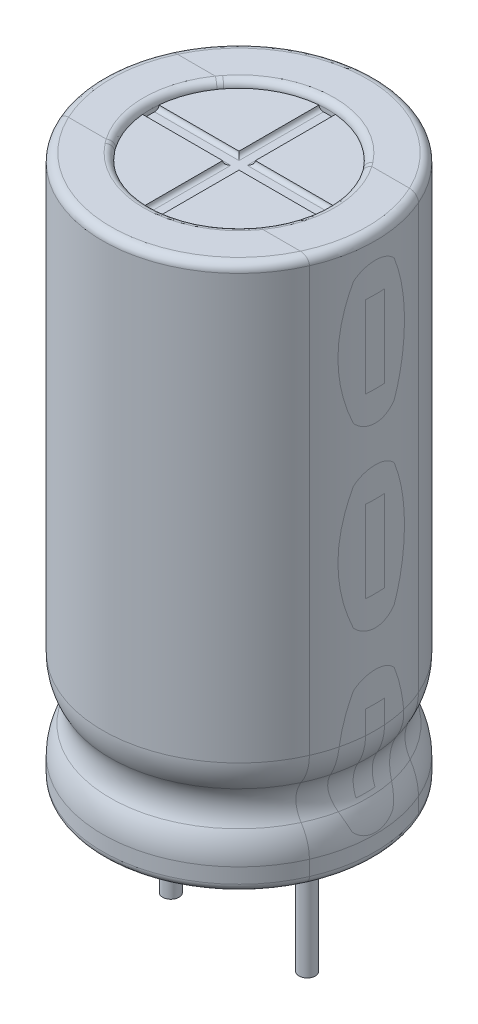
SolidWorks part; units mm, degrees
ref_plane "Front Plane" through (0, 0, 0) normal (0, 0, 1) x (1, 0, 0)
ref_plane "Top Plane" through (0, 0, 0) normal (0, 1, 0) x (1, 0, 0)
ref_plane "Right Plane" through (0, 0, 0) normal (1, 0, 0) x (0, 0, -1)
sketch "Эскиз1" plane through (0, 0, 0) normal (0, 0, 1) x (1, 0, 0)
  line L0 (0, 47.0384) -> (0, -50.5015) construction
  line L1 (0, 0) -> (-5, 0)
  line L2 (-5, 0) -> (-5, 1.5395)
  line L3 (-5, 20) -> (0, 20)
  line L4 (0, 20) -> (0, 0)
  line L5 (-5, 3.4605) -> (-5, 20)
  arc A0 (-5, 1.5395) -> (-5, 3.4605) centre (-5.8, 2.5) ccw
  dimension "D3" = 2.5
  dimension "D1" = 5
  dimension "D2" = 20
  dimension "D4" = 0.8
  dimension "D5" = 2.5
revolve "Повернуть2" add sketch "Эскиз1" angle 360 about L0
sketch "Эскиз2" plane through (0, 20, 0) normal (0, 1, 0) x (1, 0, 0)
  circle A0 centre (0, 0) radius 3.25
  dimension "D1" = 6.5
extrude "Вырез-Вытянуть1" cut sketch "Эскиз2" against normal blind 0.25
sketch "Эскиз3" plane through (0, 19.75, 0) normal (0, 1, 0) x (1, 0, 0)
  line L0 (0, 5.3403) -> (0, -5.4999) construction
  line L1 (-5.5664, 0) -> (5.593, 0) construction
  line L2 (-0.3, 3.2361) -> (-0.3, 0.3)
  line L3 (-0.3, 0.3) -> (-3.2361, 0.3)
  line L4 (0.3, 0.3) -> (3.2361, 0.3)
  line L5 (0.3, 3.2361) -> (0.3, 0.3)
  line L6 (0.3, -0.3) -> (3.2361, -0.3)
  line L7 (0.3, -3.2361) -> (0.3, -0.3)
  line L8 (-0.3, -3.2361) -> (-0.3, -0.3)
  line L9 (-0.3, -0.3) -> (-3.2361, -0.3)
  circle A0 centre (0, 0) radius 3.25 construction
  arc A1 (-3.2361, 0.3) -> (-3.2361, -0.3) centre (0, 0) ccw
  arc A2 (0.3, 3.2361) -> (-0.3, 3.2361) centre (0, 0) ccw
  arc A3 (3.2361, -0.3) -> (3.2361, 0.3) centre (0, 0) ccw
  arc A4 (-0.3, -3.2361) -> (0.3, -3.2361) centre (0, 0) ccw
  dimension "D1" = 0.3
  dimension "D2" = 0.3
extrude "Вырез-Вытянуть2" cut sketch "Эскиз3" against normal blind 0.15
fillet "Скругление1" radius 0.3 2 edges at (0, 0, 5) (0, 20, 5)
fillet "Скругление2" radius 2 2 edges at (0, 1.5395, 5) (0, 3.4605, 5)
sketch "Эскиз4" plane through (0, 0, 0) normal (0, -1, 0) x (1, 0, 0)
  line L0 (0, 5.3536) -> (0, -5.5664) construction
  line L1 (-5.8457, 0) -> (5.2871, 0) construction
  circle A1 centre (0, 0) radius 3.25
  dimension "D1" = 6.5
extrude "Вырез-Вытянуть3" cut sketch "Эскиз4" against normal blind 0.25
sketch "Эскиз5" plane through (0, 0.25, 0) normal (0, -1, 0) x (1, 0, 0)
  line L0 (0, 5.3137) -> (0, -5.593) construction
  line L1 (-5.4467, 0) -> (5.3536, 0) construction
  circle A0 centre (-2.5, 0) radius 0.3
  circle A1 centre (2.5, 0) radius 0.3
  dimension "D1" = 0.6
  dimension "D2" = 2.5
extrude "Бобышка-Вытянуть1" add sketch "Эскиз5" along normal blind 5
fillet "Скругление3" radius 0.15 8 edges at (0.3, 19.6, -1.7681) (-1.7681, 19.6, 0.3) (1.7681, 19.6, 0.3) (0.3, 19.6, 1.7681) (-0.3, 19.6, 1.7681) (1.7681, 19.6, -0.3) (-0.3, 19.6, -1.7681) (-1.7681, 19.6, -0.3)
ref_plane "Плоскость1" through (5.5, 0, 0) normal (1, 0, 0) x (0, 0, -1)
sketch "Эскиз6" plane through (5.5, 0, 0) normal (1, 0, 0) x (0, 0, -1)
  line L0 (0, 22.3182) -> (0, -7.8953) construction
  line L1 (3.25, 20) -> (-3.25, 20) construction
  line L2 (-2, 25) -> (2, 25)
  line L3 (-2, 25) -> (-2, -5)
  line L4 (-2, -5) -> (2, -5)
  line L5 (2, 25) -> (2, -5)
  line L6 (-2, 25) -> (2, -5) construction
  line L7 (-2, -5) -> (2, 25) construction
  line L19 (4.7, 20) -> (-4.7, 20) construction
  line L20 (0.35, 18) -> (-0.35, 18)
  line L30 (0.35, 18) -> (0.35, 15)
  line L31 (0.35, 15) -> (-0.35, 15)
  line L32 (-0.35, 18) -> (-0.35, 15)
  line L33 (0.35, 18) -> (-0.35, 15) construction
  line L34 (0.35, 15) -> (-0.35, 18) construction
  line L35 (0.35, 11.5) -> (0.35, 8.5)
  line L36 (0.75, 18.75) -> (-0.75, 18.75) construction
  line L37 (0.75, 18.75) -> (0.75, 14.25) construction
  line L38 (0.75, 14.25) -> (-0.75, 14.25) construction
  line L39 (-0.75, 18.75) -> (-0.75, 14.25) construction
  line L40 (0.75, 18.75) -> (-0.75, 14.25) construction
  line L41 (0.75, 14.25) -> (-0.75, 18.75) construction
  line L42 (0.35, 11.5) -> (-0.35, 11.5)
  line L43 (-0.35, 11.5) -> (-0.35, 8.5)
  line L44 (0.35, 8.5) -> (-0.35, 8.5)
  line L45 (0.35, 5) -> (0.35, 2)
  line L46 (0.35, 5) -> (-0.35, 5)
  line L47 (-0.35, 5) -> (-0.35, 2)
  line L48 (0.35, 2) -> (-0.35, 2)
  arc A0 (0.75, 18.75) -> (0.75, 14.25) centre (-4.4006, 16.5) cw
  arc A1 (-0.75, 18.75) -> (-0.75, 14.25) centre (4.4006, 16.5) ccw
  arc A2 (0.75, 18.75) -> (-0.75, 18.75) centre (0, 18.0886) ccw
  arc A3 (-0.75, 14.25) -> (0.75, 14.25) centre (0, 14.9114) ccw
  arc A4 (-0.75, 7.75) -> (0.75, 7.75) centre (0, 8.4114) ccw
  arc A5 (0.75, 12.25) -> (0.75, 7.75) centre (-4.4006, 10) cw
  arc A6 (0.75, 12.25) -> (-0.75, 12.25) centre (0, 11.5886) ccw
  arc A7 (-0.75, 12.25) -> (-0.75, 7.75) centre (4.4006, 10) ccw
  arc A8 (-0.75, 1.25) -> (0.75, 1.25) centre (0, 1.9114) ccw
  arc A9 (0.75, 5.75) -> (0.75, 1.25) centre (-4.4006, 3.5) cw
  arc A10 (0.75, 5.75) -> (-0.75, 5.75) centre (0, 5.0886) ccw
  arc A11 (-0.75, 5.75) -> (-0.75, 1.25) centre (4.4006, 3.5) ccw
  point P3 (0, 10)
  point P10 (0, 16.5)
  point P12 (0, 12.7929)
  point P18 (0, 16.5)
  point P27 (1.22, 16.5)
  point P28 (-1.22, 16.5)
  point P29 (0, 19.0886)
  point P30 (0, 13.9114)
  dimension "D9" = 0.78
  dimension "D1" = 30
  dimension "D2" = 4
  dimension "D3" = 5
  dimension "D4" = 2
  dimension "D5" = 3
  dimension "D6" = 0.7
  dimension "D7" = 4.5
  dimension "D8" = 1.5
  dimension "D10" = 0.78
  dimension "D11" = 1
  dimension "D12" = 1
  dimension "D13" = 3
split line "Разделяющая линия1"
fillet "Скругление4" radius 0.25 4 edges at (-3.25, 20, 0) (0, 20, 3.25) (3.25, 20, 0) (0, 20, -3.25)
fillet "Скругление5" radius 0.2 4 edges at (0, 0, 3.25) (-3.25, 0, 0) (0, 0, -3.25) (3.25, 0, 0)
ref_plane "Плоскость2" [suppressed] through (0, 0, 5.3) normal (0, 0, 1) x (1, 0, 0)
sketch "Эскиз7" [suppressed] plane through (0, 0, 5.3) normal (0, 0, 1) x (1, 0, 0)
  line L0 (0, 20.9995) -> (0, -1.1678) construction
  line L1 (-2.1141, 20) -> (-2.1141, 0) construction
  line L2 (3.5, 23.0802) -> (-3.5, 23.0802)
  line L3 (3.5, 23.0802) -> (3.5, -3.2485)
  line L4 (3.5, -3.2485) -> (-3.5, -3.2485)
  line L5 (-3.5, 23.0802) -> (-3.5, -3.2485)
  line L6 (3.5, 23.0802) -> (-3.5, -3.2485) construction
  line L7 (3.5, -3.2485) -> (-3.5, 23.0802) construction
  line L8 (4.2532, 20) -> (-4.2532, 20) construction
  line L9 (1.3, 20) -> (1.3, 0) construction
  line L11 (-4.2532, 0) -> (4.2532, 0) construction
  text T0 "  chang         chang" font "Open Sans" height 1.5
  text T1 "  -40+105ºC          -40+105ºC" font "Arial" height 1
  point P3 (0, 9.9159)
  dimension "D1" = 7
  dimension "D2" = 2.1141
  dimension "D3" = 1.3
split line "Разделяющая линия2" [suppressed]
